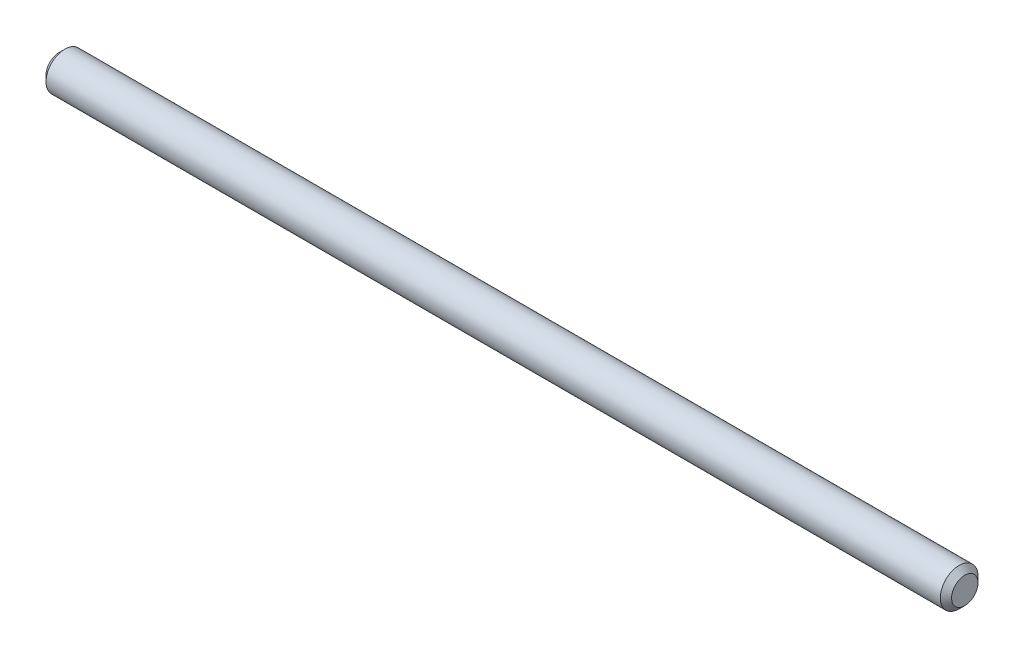
SolidWorks part; units mm, degrees
ref_plane "Front Plane" through (0, 0, 0) normal (0, 0, 1) x (1, 0, 0)
ref_plane "Top Plane" through (0, 0, 0) normal (0, 1, 0) x (1, 0, 0)
ref_plane "Right Plane" through (0, 0, 0) normal (1, 0, 0) x (0, 0, -1)
sketch "Sketch1" plane through (0, 0, 0) normal (0, 0, 1) x (1, 0, 0)
  line L0 (-76.2, 0) -> (76.2, 0) construction
  line L1 (76.2, 3.175) -> (76.2, -3.175) construction
  line L2 (-76.2, 3.175) -> (-76.2, -3.175) construction
  point P6 (71.755, -3.175)
  dimension "Thread Diameter" = 6.35
  dimension "Length" = 152.4
  dimension "D1" = 4.445
sketch "Sketch2" plane through (0, 0, 0) normal (1, 0, 0) x (0, 0, -1)
  circle A0 centre (0, 0) radius 3.175
extrude "Boss-Extrude1" add sketch "Sketch2" against normal up to vertex (76.2 mm away) and the other way up to vertex (76.2 mm away) up to point (-76.2, 0, 0) other way up to point (76.2, 0, 0)
cosmetic thread "Cosmetic Thread1" parameters "D2"=4.8387
sketch "Sketch3" plane through (76.2, 0, 0) normal (1, 0, 0) x (0, 0, -1)
  circle A1 centre (0, 0) radius 3.175
  circle A2 centre (0, 0) radius 3.175
  dimension "D1" = 0
curve "Helix/Spiral1" pitch 1.27 height 153.67 turns 121 parameters "Pitch"=1.27
chamfer "Chamfer1" distance 0.9525 angle 45 2 edges at (-76.2, 0, -3.175) (76.2, 0, -3.175)
sketch "Sketch4" plane through (0, 0, 0) normal (0, 0, 1) x (1, 0, 0)
  line L0 (76.1206, 3.3125) -> (76.7556, 2.2126) construction
  line L1 (76.7556, 2.2126) -> (77.3906, 3.3125) construction
  line L2 (77.3906, 3.3125) -> (76.1206, 3.3125) construction
  line L3 (76.7556, 3.3125) -> (76.7556, 3.175) construction
  line L4 (76.7556, 2.2126) -> (76.7556, 2.3501) construction
  line L5 (76.6762, 2.3501) -> (76.835, 2.3501) construction
  line L6 (76.2, 3.175) -> (77.3112, 3.175) construction
  line L7 (76.6762, 2.3501) -> (76.1603, 3.2437)
  line L8 (76.6762, 2.3501) -> (76.835, 2.3501)
  line L9 (76.1603, 3.2437) -> (77.3509, 3.2437)
  line L10 (77.3509, 3.2437) -> (76.835, 2.3501)
  point P13 (76.7556, 3.2437)
  dimension "D2" = 0.1588
sweep "Cut-Sweep3" [suppressed] cut profiles "Sketch4" path "Helix/Spiral1"
ref_axis "Axis1" through (0, -3.4925, 0) along (0, 1, 0)
equation "\"D3@Helix/Spiral1\" = \"Length@Sketch1\"+\"Pitch@Helix/Spiral1\""
equation "\"D1@Chamfer1\" = \"Pitch@Helix/Spiral1\"*.75"
equation "\"D1@Sketch4\" = \"Pitch@Helix/Spiral1\""
equation "\"D2@Sketch4\" = \"D1@Sketch4\"/8"
equation "\"D1@Sketch1\" = \"Pitch@Helix/Spiral1\"*3.50"
